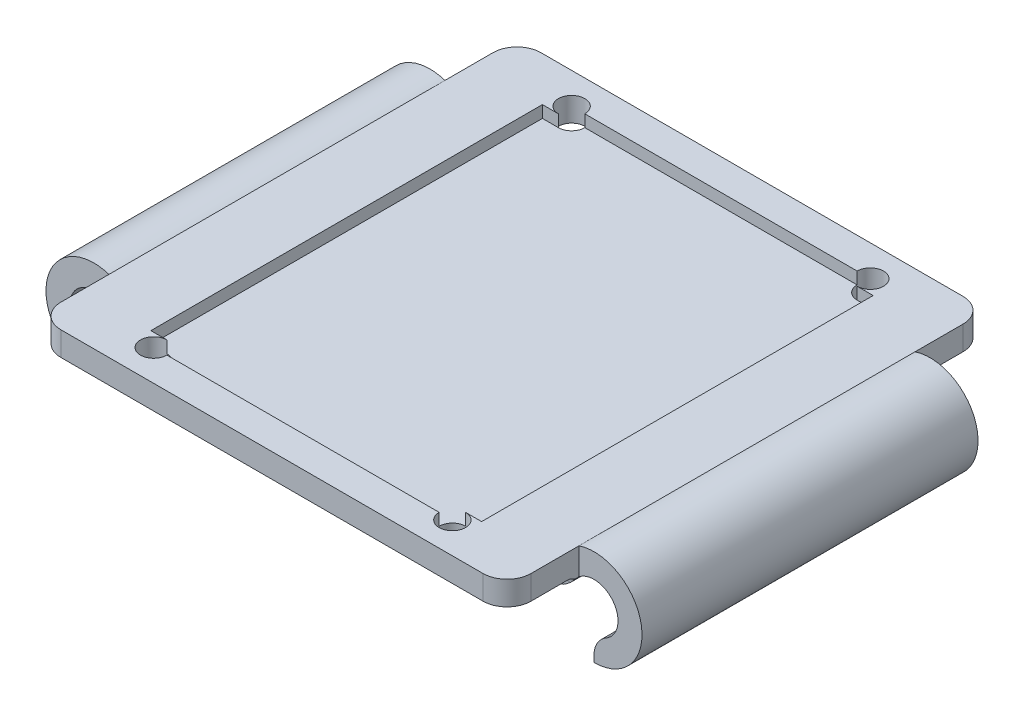
SolidWorks part; units mm, degrees
ref_plane "前视基准面" through (0, 0, 0) normal (0, 0, 1) x (1, 0, 0)
ref_plane "上视基准面" through (0, 0, 0) normal (0, 1, 0) x (1, 0, 0)
ref_plane "右视基准面" through (0, 0, 0) normal (1, 0, 0) x (0, 0, -1)
sketch "草图1" plane through (0, 0, 0) normal (0, 0, 1) x (1, 0, 0)
  line L0 (72.7521, 22.4325) -> (31.0821, 22.4325) construction
  line L1 (72.7521, 20.4325) -> (72.7521, 18.4325)
  line L2 (72.7521, 23.9325) -> (31.0821, 23.9325) construction
  line L3 (72.7521, 23.9325) -> (72.7521, 20.9325) construction
  line L4 (72.7521, 20.9325) -> (31.0821, 20.9325) construction
  line L5 (31.0821, 23.9325) -> (31.0821, 20.9325) construction
  line L6 (72.7521, 23.9325) -> (31.0821, 20.9325) construction
  line L7 (72.7521, 20.9325) -> (31.0821, 23.9325) construction
  line L8 (69.044, 23.9325) -> (34.7902, 23.9325)
  line L9 (68.7521, 22.4325) -> (35.0821, 22.4325)
  line L10 (31.0821, 20.4325) -> (31.0821, 18.4325)
  circle A0 centre (72.7521, 22.4325) radius 2 construction
  circle A1 centre (31.0821, 22.4325) radius 2 construction
  circle A2 centre (72.7521, 22.4325) radius 4 construction
  circle A3 centre (31.0821, 22.4325) radius 4 construction
  arc A4 (72.7521, 20.4325) -> (71.3208, 23.8294) centre (72.7521, 22.4325) ccw
  arc A5 (72.7521, 18.4325) -> (69.044, 23.9325) centre (72.7521, 22.4325) ccw
  arc A6 (71.3208, 23.8294) -> (71.1521, 23.6325) centre (72.7521, 22.4325) ccw
  arc A7 (34.7902, 23.9325) -> (31.0821, 18.4325) centre (31.0821, 22.4325) ccw
  arc A8 (32.6821, 23.6325) -> (31.0821, 20.4325) centre (31.0821, 22.4325) ccw
  arc A9 (35.0821, 22.4325) -> (32.6821, 23.6325) centre (35.0821, 25.4325) cw
  arc A10 (71.1521, 23.6325) -> (68.7521, 22.4325) centre (68.7521, 25.4325) cw
  point P6 (51.9171, 22.4325)
  point P25 (0, 0)
  point P26 (0, 0)
  point P27 (0, 0)
  point P28 (0, 0)
  point P29 (0, 0)
  point P30 (0, 0)
  point P33 (33.0821, 22.4325)
  point P36 (70.7521, 22.4325)
  dimension "D1" = 41.67
  dimension "D2" = 8
  dimension "D3" = 4
  dimension "D4" = 4
  dimension "D5" = 8
  dimension "D7" = 3
  dimension "D8" = 3
  dimension "D6" = 3
extrude "凸台-拉伸1" add sketch "草图1" along normal blind 28
sketch "草图2" plane through (0, 0, 28) normal (0, 0, 1) x (1, 0, 0)
  line L0 (36.033, 26.2325) -> (72.2894, 26.2325) construction
  line L1 (35.0821, 22.4325) -> (68.7521, 22.4325) construction
  line L2 (32.3311, 26.2325) -> (71.8047, 26.2325)
  line L3 (71.8047, 26.2325) -> (69.9484, 23.2922)
  line L4 (69.9484, 23.2922) -> (34.6282, 23.2922)
  line L5 (34.6282, 23.2922) -> (32.1673, 26.2325)
  line L6 (32.1673, 26.2325) -> (32.3311, 26.2325)
  arc A0 (34.7902, 23.9325) -> (31.0821, 18.4325) centre (31.0821, 22.4325) ccw construction
  dimension "D1" = 3.8
extrude "凸台-拉伸2" add sketch "草图2" against normal up to surface (28 mm away) up to face at (51.9171, 22.6719, 0)
sketch "草图3" plane through (0, 26.2325, 0) normal (0, 1, 0) x (1, 0, 0)
  line L0 (32.3311, -14) -> (69.4432, -14) construction
  line L1 (32.3311, 0) -> (71.5031, 0) construction
  line L2 (51.9171, -1.3937) -> (51.9171, -5.6688) construction
  line L4 (71.5031, -28) -> (32.3311, -28) construction
  line L5 (71.5031, 6) -> (32.3311, 6)
  line L6 (71.5031, 6) -> (71.5031, -34)
  line L7 (71.5031, -34) -> (32.3311, -34)
  line L8 (32.3311, 6) -> (32.3311, -34)
  line L9 (71.5031, 6) -> (32.3311, -34) construction
  line L10 (71.5031, -34) -> (32.3311, 6) construction
  point P2 (51.9171, -14)
  dimension "D1" = 6
  dimension "D2" = 6
extrude "凸台-拉伸3" add sketch "草图3" against normal blind 2
fillet "圆角1" radius 2 4 edges at (71.5031, 25.2325, -6) (32.3311, 25.2325, -6) (32.3311, 25.2325, 34) (71.5031, 25.2325, 34)
fillet "圆角2" radius 1 2 edges at (51.9171, 24.2325, 28) (51.9171, 24.2325, 0)
fillet "圆角3" radius 2 2 edges at (72.7521, 20.4325, 14) (31.0821, 20.4325, 14)
sketch "草图4" plane through (0, 26.2325, 0) normal (0, 1, 0) x (1, 0, 0)
  line L0 (51.9171, 6) -> (51.9171, -34) construction
  line L1 (69.5031, 6) -> (34.3311, 6) construction
  line L2 (34.3311, -34) -> (69.5031, -34) construction
  line L4 (39.4721, 3.415) -> (64.3621, 3.415) construction
  line L5 (39.4721, 3.415) -> (39.4721, -31.415) construction
  line L6 (39.4721, -31.415) -> (64.3621, -31.415) construction
  line L7 (64.3621, 3.415) -> (64.3621, -31.415) construction
  line L8 (39.4721, 3.415) -> (64.3621, -31.415) construction
  line L9 (39.4721, -31.415) -> (64.3621, 3.415) construction
  circle A0 centre (39.4721, 3.415) radius 1.1
  circle A1 centre (64.3621, 3.415) radius 1.1
  circle A2 centre (64.3621, -31.415) radius 1.1
  circle A3 centre (39.4721, -31.415) radius 1.1
  point P6 (51.9171, -14)
  dimension "D1" = 24.89
  dimension "D2" = 34.83
extrude "切除-拉伸1" cut sketch "草图4" against normal blind 2
sketch "草图5" plane through (0, 26.2325, 0) normal (0, 1, 0) x (1, 0, 0)
  line L0 (51.9171, 6) -> (51.9171, -34) construction
  line L1 (69.5031, 6) -> (34.3311, 6) construction
  line L2 (34.3311, -34) -> (69.5031, -34) construction
  line L3 (39.4721, -30.315) -> (38.1363, -30.315)
  line L4 (38.1363, 5.6551) -> (65.6979, 5.6551) construction
  line L5 (38.1363, 5.6551) -> (38.1363, -32.9184) construction
  line L6 (38.1363, -32.9184) -> (65.6979, -32.9184) construction
  line L7 (65.6979, 5.6551) -> (65.6979, -32.9184) construction
  line L8 (38.1363, 5.6551) -> (65.6979, -32.9184) construction
  line L9 (38.1363, -32.9184) -> (65.6979, 5.6551) construction
  line L10 (38.1363, -30.315) -> (38.1363, 2.315)
  line L11 (38.1363, 2.315) -> (39.4721, 2.315)
  line L12 (40.5721, 3.415) -> (63.2621, 3.415)
  line L14 (63.2621, -31.415) -> (40.5721, -31.415)
  line L15 (64.3621, -30.315) -> (65.6979, -30.315)
  line L16 (65.6979, -30.315) -> (65.6979, 2.315)
  line L17 (65.6979, 2.315) -> (64.3621, 2.315)
  arc A0 (39.4721, -30.315) -> (40.5721, -31.415) centre (39.4721, -31.415) cw
  circle A1 centre (39.4721, -31.415) radius 1.1 construction
  circle A2 centre (39.4721, 3.415) radius 1.1 construction
  arc A3 (39.4721, 2.315) -> (40.5721, 3.415) centre (39.4721, 3.415) ccw
  circle A4 centre (64.3621, 3.415) radius 1.1 construction
  arc A5 (63.2621, 3.415) -> (64.3621, 2.315) centre (64.3621, 3.415) ccw
  circle A6 centre (64.3621, -31.415) radius 1.1 construction
  arc A7 (64.3621, -30.315) -> (63.2621, -31.415) centre (64.3621, -31.415) ccw
  point P6 (51.9171, -13.6316)
extrude "切除-拉伸2" cut sketch "草图5" against normal blind 1
